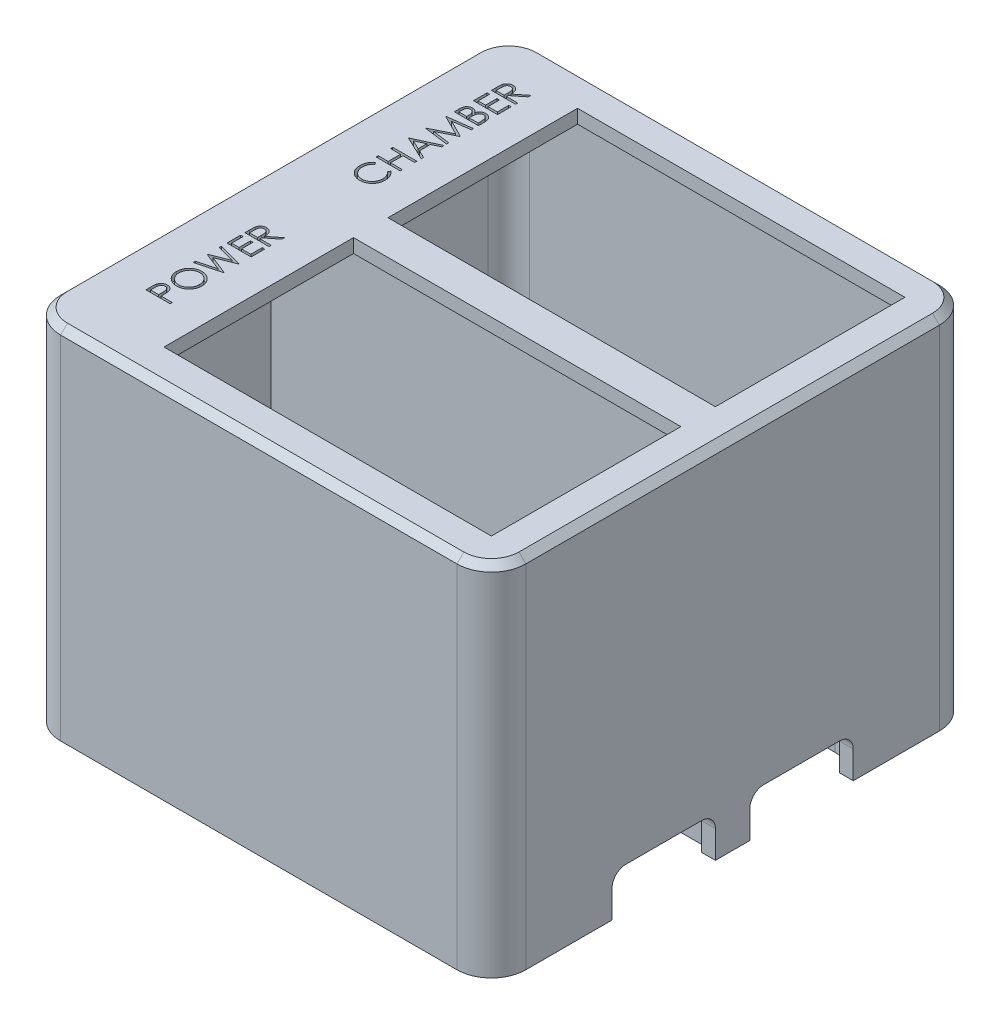
SolidWorks part; units mm, degrees
ref_plane "Front Plane" through (0, 0, 0) normal (0, 0, 1) x (1, 0, 0)
ref_plane "Top Plane" through (0, 0, 0) normal (0, 1, 0) x (1, 0, 0)
ref_plane "Right Plane" through (0, 0, 0) normal (1, 0, 0) x (0, 0, -1)
sketch "Sketch2" plane through (0, 0, 0) normal (0, 1, 0) x (1, 0, 0)
  line L0 (-33.75, 0) -> (33.75, 0) construction
  line L1 (-33.75, 35) -> (33.75, 35)
  line L2 (-33.75, 35) -> (-33.75, -35)
  line L3 (-33.75, -35) -> (33.75, -35)
  line L4 (33.75, 35) -> (33.75, -35)
  line L7 (-18.75, -2.5) -> (28.75, -2.5)
  line L8 (-18.75, -2.5) -> (-18.75, -30)
  line L9 (-18.75, -30) -> (28.75, -30)
  line L10 (28.75, -2.5) -> (28.75, -30)
  line L11 (-18.75, 30) -> (28.75, 30)
  line L12 (-18.75, 30) -> (-18.75, 2.5)
  line L13 (-18.75, 2.5) -> (28.75, 2.5)
  line L14 (28.75, 30) -> (28.75, 2.5)
  point P0 (0, 0)
  point P5 (0, 0)
  dimension "D1" = 5
  dimension "D2" = 47.5
  dimension "D3" = 27.5
  dimension "D4" = 15
  dimension "D5" = 5
  dimension "D6" = 5
  dimension "D7" = 5
extrude "Boss-Extrude1" add sketch "Sketch2" along normal blind 2
sketch "Sketch3" plane through (0, 0, 0) normal (0, -1, 0) x (1, 0, 0)
  line L0 (-31.75, -1.5) -> (-31.75, -33)
  line L1 (-31.75, 1.5) -> (31.75, 1.5)
  line L3 (-31.75, -1.5) -> (31.75, -1.5)
  line L5 (-31.75, 1.5) -> (31.75, -1.5) construction
  line L6 (-31.75, -1.5) -> (31.75, 1.5) construction
  line L7 (31.75, 1.5) -> (31.75, 33)
  line L8 (31.75, -33) -> (31.75, 33)
  line L9 (31.75, 33) -> (-31.75, 33)
  line L10 (-31.75, 33) -> (-31.75, -33)
  line L11 (-31.75, -33) -> (31.75, -33)
  line L12 (31.75, -33) -> (31.75, -1.5)
  line L13 (31.75, 33) -> (-31.75, 33)
  line L14 (-31.75, 33) -> (-31.75, 1.5)
  line L15 (-31.75, -33) -> (31.75, -33)
  line L16 (33.75, -35) -> (33.75, 35)
  line L17 (33.75, 35) -> (-33.75, 35)
  line L18 (-33.75, 35) -> (-33.75, -35)
  line L19 (-33.75, -35) -> (33.75, -35)
  line L20 (33.75, -35) -> (33.75, 35)
  line L21 (33.75, 35) -> (-33.75, 35)
  line L22 (-33.75, 35) -> (-33.75, -35)
  line L23 (-33.75, -35) -> (33.75, -35)
  point P2 (0, 0)
  dimension "D3" = 3
  dimension "D1" = 2
  dimension "D2" = 0
extrude "Boss-Extrude2" add sketch "Sketch3" along normal blind 50
fillet "Fillet1" radius 3 4 edges at (-31.75, -25, 33) (31.75, -25, -33) (-31.75, -25, -33) (31.75, -25, 33)
fillet "Fillet2" radius 5 4 edges at (-33.75, -24, 35) (-33.75, -24, -35) (33.75, -24, -35) (33.75, -24, 35)
sketch "Sketch4" plane through (33.75, 0, 1.75) normal (-1, 0, 0) x (0, 0, 1)
  line L0 (0.75, -50) -> (0.75, -44)
  line L2 (0.75, -44) -> (15.75, -44)
  line L3 (15.75, -44) -> (15.75, -50)
  line L4 (15.75, -50) -> (0.75, -50)
  line L6 (-31.75, -50) -> (28.25, -50) construction
  line L7 (8.25, 2) -> (8.25, -44) construction
  line L8 (28.25, 2) -> (-31.75, 2) construction
  line L11 (-1.75, -55) -> (-1.75, 55) construction
  line L12 (-19.25, -50) -> (-4.25, -50)
  line L13 (-19.25, -44) -> (-19.25, -50)
  line L14 (-4.25, -44) -> (-19.25, -44)
  line L15 (-4.25, -50) -> (-4.25, -44)
  point P2 (0, 0)
  point P14 (0, 0)
  point P15 (0, 0)
  dimension "D1" = 6
  dimension "D2" = 15
  dimension "D3" = 5
extrude "Cut-Extrude1" cut sketch "Sketch4" along normal blind 4
chamfer "Chamfer1" distance 1 angle 45 8 edges at (-32.2855, 2, -33.5355) (-33.75, 2, 0) (0, 2, -35) (-32.2855, 2, 33.5355) (32.2855, 2, -33.5355) (0, 2, 35) (33.75, 2, 0) (32.2855, 2, 33.5355)
sketch "Sketch6" plane through (0, -50, 0) normal (0, -1, 0) x (1, 0, 0)
  line L0 (-33.75, 30) -> (-33.75, -30) construction
  line L1 (-33.75, 27.75) -> (-18.75, 27.75)
  line L2 (-33.75, 27.75) -> (-33.75, 19.75)
  line L3 (-33.75, 19.75) -> (-18.75, 19.75)
  line L4 (-18.75, 27.75) -> (-18.75, 19.75)
  line L5 (-18.75, 23.75) -> (-33.75, 23.75) construction
  line L6 (28.75, 30) -> (28.75, 2.5) construction
  line L8 (-18.75, 23.75) -> (28.75, 23.75) construction
  line L10 (-33.75, 27.75) -> (-18.75, 27.75)
  line L11 (-33.75, 19.75) -> (-18.75, 19.75)
  line L12 (0, -55) -> (0, 55) construction
  line L14 (33.75, 19.75) -> (18.75, 19.75)
  line L15 (33.75, 27.75) -> (18.75, 27.75)
  line L16 (18.75, 27.75) -> (18.75, 19.75)
  line L17 (33.75, 19.75) -> (18.75, 19.75)
  line L18 (33.75, 27.75) -> (33.75, 19.75)
  line L19 (33.75, 27.75) -> (18.75, 27.75)
  circle A0 centre (-23.75, 23.75) radius 1.75
  circle A1 centre (23.75, 23.75) radius 1.75
  point P6 (0, 0)
  point P7 (0, 0)
  point P14 (28.75, 20.5905)
  point P18 (27.557, 16.5)
  point P20 (0, 0)
  line M11 (-31.75, 1.5) -> (-31.75, 30)
  line M26 (31.75, 2.5) -> (31.75, 1.5)
  dimension "D3" = 5
  dimension "D4" = 3.5
  dimension "D1" = 15
  dimension "D2" = 8
  dimension "D5" = 23.75
extrude "Boss-Extrude3" add sketch "Sketch6" against normal blind 2.5 contours L4 L1 L3 A0 M11 | L15 L16 L14 A1 M26 region at (-25.25, -50, 27.5974) region at (26.4679, -50, 23.75)
mirror "Mirror1" about plane through (0, 0, 0) normal (0, 0, 1) of "Boss-Extrude3"
fillet "Fillet4" radius 3 16 edges at (-18.75, -48.75, 19.75) (-31.75, -48.75, 19.75) (-31.75, -48.75, 27.75) (-18.75, -48.75, 27.75) (-18.75, -48.75, -19.75) (-18.75, -48.75, -27.75) (31.75, -48.75, -19.75) (-31.75, -48.75, -27.75) (-31.75, -48.75, -19.75) (31.75, -48.75, -27.75) (18.75, -48.75, -27.75) (18.75, -48.75, -19.75) (31.75, -48.75, 19.75) (31.75, -48.75, 27.75) (18.75, -48.75, 27.75) (18.75, -48.75, 19.75)
sketch "Sketch7" plane through (0, 2, 0) normal (0, 1, 0) x (1, 0, 0)
  line L0 (-23.75, 34) -> (-23.75, -34) construction
  line L1 (28.75, 34) -> (-28.75, 34) construction
  line L2 (-28.75, -34) -> (28.75, -34) construction
  line L3 (-18.75, 30) -> (-18.75, 2.5) construction
  text T0 "   POWER         CHAMBER"
  dimension "4" = 5
extrude "Cut-Extrude2" cut sketch "Sketch7" against normal blind 1
fillet "Fillet5" radius 2 4 edges at (32.75, -44, -2.5) (32.75, -44, 17.5) (32.75, -44, 2.5) (32.75, -44, -17.5)
